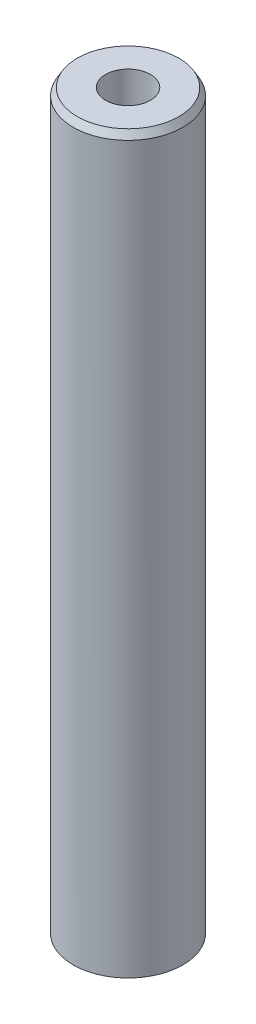
SolidWorks part; units mm, degrees
ref_plane "Front Plane" through (0, 0, 0) normal (0, 0, 1) x (1, 0, 0)
ref_plane "Top Plane" through (0, 0, 0) normal (0, 1, 0) x (1, 0, 0)
ref_plane "Right Plane" through (0, 0, 0) normal (1, 0, 0) x (0, 0, -1)
sketch "Sketch1" plane through (0, 0, 0) normal (0, 1, 0) x (1, 0, 0)
  circle A0 centre (0, 0) radius 37.5
  dimension "SHAFT_OD" = 75
extrude "Boss-Extrude1" add sketch "Sketch1" along normal blind 503.5594
sketch "Sketch2" plane through (0, 0, 0) normal (0, 1, 0) x (1, 0, 0)
  circle A0 centre (0, 0) radius 15.3454
  dimension "BORE_D" = 30.6908
extrude "Cut-Extrude1" cut sketch "Sketch2" along normal through all
chamfer "Chamfer1" distance 4.8947 angle 30 2 edges at (0, 503.5594, 37.5) (0, 0, 37.5) first distance on face at (0, 503.5594, 37.5) first distance on face at (0, 0, 15.3454)
